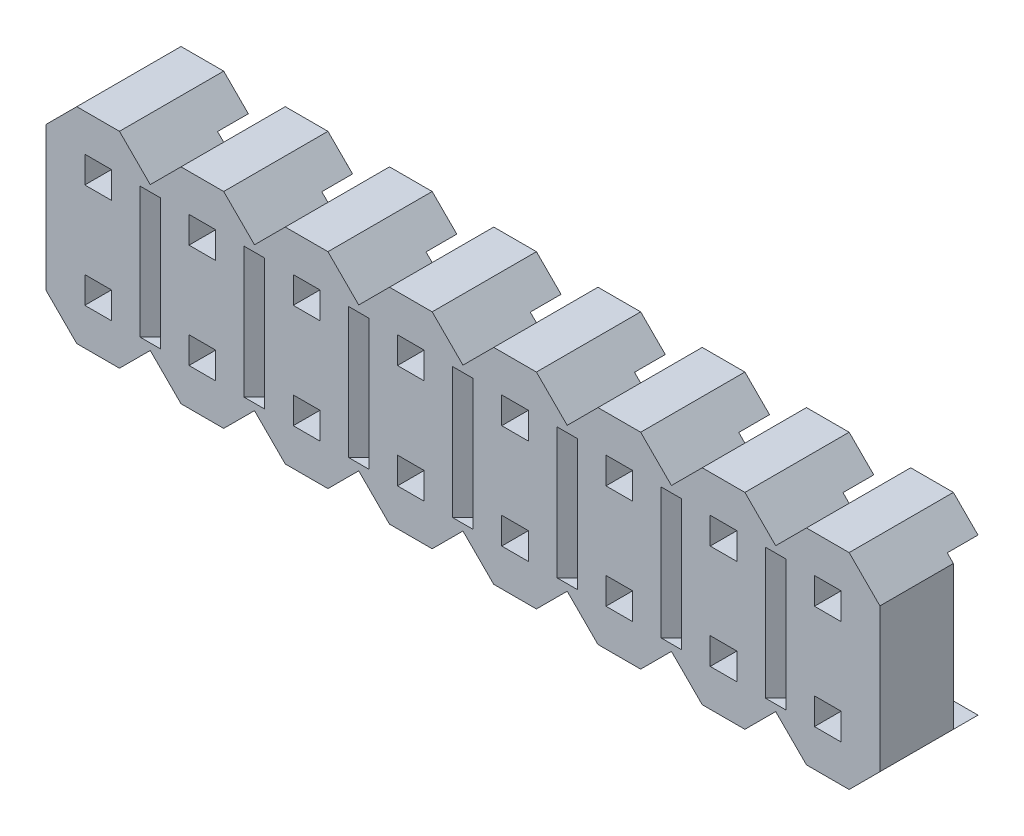
SolidWorks part; units mm, degrees
ref_plane "Front" through (0, 0, 0) normal (0, 0, 1) x (1, 0, 0)
ref_plane "Top" through (0, 0, 0) normal (0, 1, 0) x (1, 0, 0)
ref_plane "Right" through (0, 0, 0) normal (1, 0, 0) x (0, 0, -1)
sketch "Sketch1" plane through (0, 0, 0) normal (0, 0, 1) x (1, 0, 0)
  line L0 (-1.27, 1.75) -> (-1.27, -1.75)
  line L1 (-0.52, 2.5) -> (0.52, 2.5)
  line L2 (-0.52, -2.5) -> (0.52, -2.5)
  line L3 (1.27, 1.75) -> (2.02, 2.5)
  line L4 (2.02, 2.5) -> (3.06, 2.5)
  line L5 (0.52, 2.5) -> (1.27, 1.75)
  line L6 (-1.27, 1.75) -> (-0.52, 2.5)
  line L7 (-0.52, -2.5) -> (-1.27, -1.75)
  line L8 (1.27, -1.75) -> (0.52, -2.5)
  line L9 (3.06, 2.5) -> (3.81, 1.75)
  line L10 (2.865, 1.595) -> (2.215, 1.595)
  line L11 (2.215, 1.595) -> (2.215, 0.945)
  line L12 (2.865, 0.945) -> (2.865, 1.595)
  line L13 (-0.325, 0.945) -> (0.325, 0.945)
  line L14 (0.325, 0.945) -> (0.325, 1.595)
  line L15 (0.325, 1.595) -> (-0.325, 1.595)
  line L16 (-0.325, 1.595) -> (-0.325, 0.945)
  line L17 (-0.325, -0.945) -> (0.325, -0.945)
  line L18 (0.325, -0.945) -> (0.325, -1.595)
  line L19 (0.325, -1.595) -> (-0.325, -1.595)
  line L20 (-0.325, -1.595) -> (-0.325, -0.945)
  line L21 (2.215, 0.945) -> (2.865, 0.945)
  line L22 (2.215, -0.945) -> (2.865, -0.945)
  line L23 (2.215, -1.595) -> (2.215, -0.945)
  line L24 (2.865, -1.595) -> (2.215, -1.595)
  line L25 (2.865, -0.945) -> (2.865, -1.595)
  line L26 (3.81, -1.75) -> (3.06, -2.5)
  line L27 (2.02, -2.5) -> (3.06, -2.5)
  line L28 (2.02, -2.5) -> (1.27, -1.75)
  line L29 (3.81, 1.75) -> (4.56, 2.5)
  line L30 (4.56, 2.5) -> (5.6, 2.5)
  line L31 (5.6, 2.5) -> (6.35, 1.75)
  line L32 (5.405, 1.595) -> (4.755, 1.595)
  line L33 (4.755, 1.595) -> (4.755, 0.945)
  line L34 (5.405, 0.945) -> (5.405, 1.595)
  line L35 (4.755, 0.945) -> (5.405, 0.945)
  line L36 (4.755, -0.945) -> (5.405, -0.945)
  line L37 (4.755, -1.595) -> (4.755, -0.945)
  line L38 (5.405, -1.595) -> (4.755, -1.595)
  line L39 (5.405, -0.945) -> (5.405, -1.595)
  line L40 (6.35, -1.75) -> (5.6, -2.5)
  line L41 (4.56, -2.5) -> (5.6, -2.5)
  line L42 (4.56, -2.5) -> (3.81, -1.75)
  line L43 (6.35, 1.75) -> (7.1, 2.5)
  line L44 (7.1, 2.5) -> (8.14, 2.5)
  line L45 (8.14, 2.5) -> (8.89, 1.75)
  line L46 (7.945, 1.595) -> (7.295, 1.595)
  line L47 (7.295, 1.595) -> (7.295, 0.945)
  line L48 (7.945, 0.945) -> (7.945, 1.595)
  line L49 (7.295, 0.945) -> (7.945, 0.945)
  line L50 (7.295, -0.945) -> (7.945, -0.945)
  line L51 (7.295, -1.595) -> (7.295, -0.945)
  line L52 (7.945, -1.595) -> (7.295, -1.595)
  line L53 (7.945, -0.945) -> (7.945, -1.595)
  line L54 (8.89, -1.75) -> (8.14, -2.5)
  line L55 (7.1, -2.5) -> (8.14, -2.5)
  line L56 (7.1, -2.5) -> (6.35, -1.75)
  line L57 (8.89, 1.75) -> (9.64, 2.5)
  line L58 (9.64, 2.5) -> (10.68, 2.5)
  line L59 (10.68, 2.5) -> (11.43, 1.75)
  line L60 (10.485, 1.595) -> (9.835, 1.595)
  line L61 (9.835, 1.595) -> (9.835, 0.945)
  line L62 (10.485, 0.945) -> (10.485, 1.595)
  line L63 (9.835, 0.945) -> (10.485, 0.945)
  line L64 (9.835, -0.945) -> (10.485, -0.945)
  line L65 (9.835, -1.595) -> (9.835, -0.945)
  line L66 (10.485, -1.595) -> (9.835, -1.595)
  line L67 (10.485, -0.945) -> (10.485, -1.595)
  line L68 (11.43, -1.75) -> (10.68, -2.5)
  line L69 (9.64, -2.5) -> (10.68, -2.5)
  line L70 (9.64, -2.5) -> (8.89, -1.75)
  line L71 (11.43, 1.75) -> (12.18, 2.5)
  line L72 (12.18, 2.5) -> (13.22, 2.5)
  line L73 (13.22, 2.5) -> (13.97, 1.75)
  line L74 (13.025, 1.595) -> (12.375, 1.595)
  line L75 (12.375, 1.595) -> (12.375, 0.945)
  line L76 (13.025, 0.945) -> (13.025, 1.595)
  line L77 (12.375, 0.945) -> (13.025, 0.945)
  line L78 (12.375, -0.945) -> (13.025, -0.945)
  line L79 (12.375, -1.595) -> (12.375, -0.945)
  line L80 (13.025, -1.595) -> (12.375, -1.595)
  line L81 (13.025, -0.945) -> (13.025, -1.595)
  line L82 (13.97, -1.75) -> (13.22, -2.5)
  line L83 (12.18, -2.5) -> (13.22, -2.5)
  line L84 (12.18, -2.5) -> (11.43, -1.75)
  line L85 (13.97, 1.75) -> (14.72, 2.5)
  line L86 (14.72, 2.5) -> (15.76, 2.5)
  line L87 (15.76, 2.5) -> (16.51, 1.75)
  line L88 (15.565, 1.595) -> (14.915, 1.595)
  line L89 (14.915, 1.595) -> (14.915, 0.945)
  line L90 (15.565, 0.945) -> (15.565, 1.595)
  line L91 (14.915, 0.945) -> (15.565, 0.945)
  line L92 (14.915, -0.945) -> (15.565, -0.945)
  line L93 (14.915, -1.595) -> (14.915, -0.945)
  line L94 (15.565, -1.595) -> (14.915, -1.595)
  line L95 (15.565, -0.945) -> (15.565, -1.595)
  line L96 (16.51, -1.75) -> (15.76, -2.5)
  line L97 (14.72, -2.5) -> (15.76, -2.5)
  line L98 (14.72, -2.5) -> (13.97, -1.75)
  line L99 (16.51, 1.75) -> (17.26, 2.5)
  line L100 (17.26, 2.5) -> (18.3, 2.5)
  line L101 (18.3, 2.5) -> (19.05, 1.75)
  line L102 (18.105, 1.595) -> (17.455, 1.595)
  line L103 (17.455, 1.595) -> (17.455, 0.945)
  line L104 (18.105, 0.945) -> (18.105, 1.595)
  line L105 (17.455, 0.945) -> (18.105, 0.945)
  line L106 (17.455, -0.945) -> (18.105, -0.945)
  line L107 (17.455, -1.595) -> (17.455, -0.945)
  line L108 (18.105, -1.595) -> (17.455, -1.595)
  line L109 (18.105, -0.945) -> (18.105, -1.595)
  line L110 (19.05, -1.75) -> (18.3, -2.5)
  line L111 (17.26, -2.5) -> (18.3, -2.5)
  line L112 (17.26, -2.5) -> (16.51, -1.75)
  line L126 (19.05, 1.75) -> (19.05, -1.75)
extrude "Основание" add sketch "Sketch1" along normal blind 2.54
sketch "Sketch6" plane through (0, 0, 0) normal (0, 0, -1) x (-1, 0, 0)
  line L0 (-19.05, 1.9) -> (1.27, 1.9)
  line L1 (-19.05, -1.75) -> (-19.05, 1.75) construction
  line L2 (1.27, 1.75) -> (1.27, -1.75) construction
  line L3 (-19.05, -1.9) -> (1.27, -1.9)
  line L4 (-19.05, 1.9) -> (-19.05, -1.9)
  line L5 (1.27, 1.9) -> (1.27, -1.9)
extrude "Нижний вырез" cut sketch "Sketch6" against normal blind 0.75
sketch "Sketch7" plane through (0, 0, 2.54) normal (0, 0, 1) x (1, 0, 0)
  line L0 (1.02, 1.595) -> (1.52, 1.595)
  line L1 (1.52, 1.595) -> (1.52, -1.592)
  line L2 (1.02, 1.595) -> (1.02, -1.592)
  line L3 (1.02, -1.592) -> (1.52, -1.592)
  line L4 (3.56, 1.595) -> (4.06, 1.595)
  line L5 (4.06, 1.595) -> (4.06, -1.592)
  line L6 (3.56, 1.595) -> (3.56, -1.592)
  line L7 (3.56, -1.592) -> (4.06, -1.592)
  line L8 (6.1, 1.595) -> (6.6, 1.595)
  line L9 (6.6, 1.595) -> (6.6, -1.592)
  line L10 (6.1, 1.595) -> (6.1, -1.592)
  line L11 (6.1, -1.592) -> (6.6, -1.592)
  line L12 (8.64, 1.595) -> (9.14, 1.595)
  line L13 (9.14, 1.595) -> (9.14, -1.592)
  line L14 (8.64, 1.595) -> (8.64, -1.592)
  line L15 (8.64, -1.592) -> (9.14, -1.592)
  line L16 (11.18, 1.595) -> (11.68, 1.595)
  line L17 (11.68, 1.595) -> (11.68, -1.592)
  line L18 (11.18, 1.595) -> (11.18, -1.592)
  line L19 (11.18, -1.592) -> (11.68, -1.592)
  line L20 (13.72, 1.595) -> (14.22, 1.595)
  line L21 (14.22, 1.595) -> (14.22, -1.592)
  line L22 (13.72, 1.595) -> (13.72, -1.592)
  line L23 (13.72, -1.592) -> (14.22, -1.592)
  line L24 (16.26, 1.595) -> (16.76, 1.595)
  line L25 (16.76, 1.595) -> (16.76, -1.592)
  line L26 (16.26, 1.595) -> (16.26, -1.592)
  line L27 (16.26, -1.592) -> (16.76, -1.592)
extrude "Верхние надломы" cut sketch "Sketch7" against normal blind 0.25
chamfer "Chamfer1" distance 0.25 angle 45
